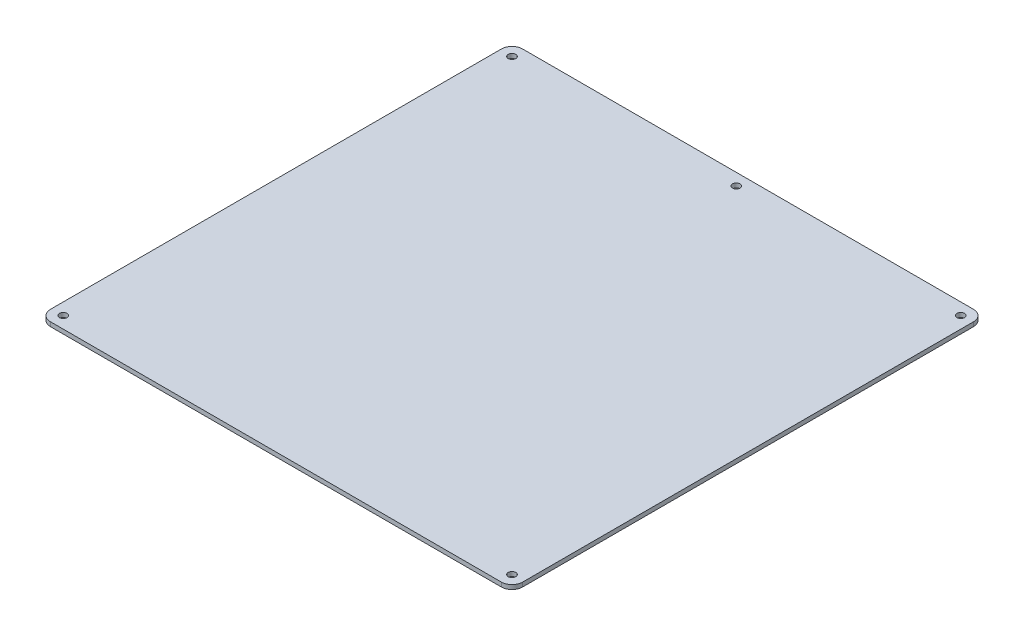
SolidWorks part; units mm, degrees
material "1060-H12"
ref_plane "Front" through (0, 0, 0) normal (0, 0, 1) x (1, 0, 0)
ref_plane "Top" through (0, 0, 0) normal (0, 1, 0) x (1, 0, 0)
ref_plane "Right" through (0, 0, 0) normal (1, 0, 0) x (0, 0, -1)
sketch "Эскиз1" plane through (0, 0, 0) normal (0, 1, 0) x (1, 0, 0)
  line L1 (-105, 110) -> (105, 110)
  line L2 (-110, 105) -> (-110, -105)
  line L3 (-105, -110) -> (105, -110)
  line L4 (110, 105) -> (110, -105)
  line L5 (-110, 110) -> (110, -110) construction
  line L6 (-110, -110) -> (110, 110) construction
  line L11 (-100, -100) -> (100, 100) construction
  line L12 (-100, 100) -> (100, -100) construction
  circle A0 centre (104.5, 104.5) radius 1.75
  circle A1 centre (104.5, -104.5) radius 1.75
  circle A2 centre (0, 104.5) radius 1.75
  circle A3 centre (-104.5, 104.5) radius 1.75
  circle A4 centre (-104.5, -104.5) radius 1.75
  arc A5 (-110, -105) -> (-105, -110) centre (-105, -105) ccw
  arc A6 (105, -110) -> (110, -105) centre (105, -105) ccw
  arc A7 (105, 110) -> (110, 105) centre (105, 105) cw
  arc A8 (-110, 105) -> (-105, 110) centre (-105, 105) cw
  point P0 (0, 0)
  point P28 (0, 0)
  dimension "D3" = 3.5
  dimension "D4" = 3.5
  dimension "D6" = 209
  dimension "D7" = 3.5
  dimension "D8" = 3.5
  dimension "D9" = 5.5
  dimension "D10" = 5.5
  dimension "D12" = 3.5
  dimension "D13" = 5.5
  dimension "D14" = 5.5
  dimension "D15" = 5
  dimension "D1" = 220
  dimension "D2" = 220
  dimension "D5" = 5.5
  dimension "D11" = 5.5
  dimension "D16" = 200
  dimension "D17" = 200
extrude "Бобышка-Вытянуть1" add sketch "Эскиз1" along normal blind 2
